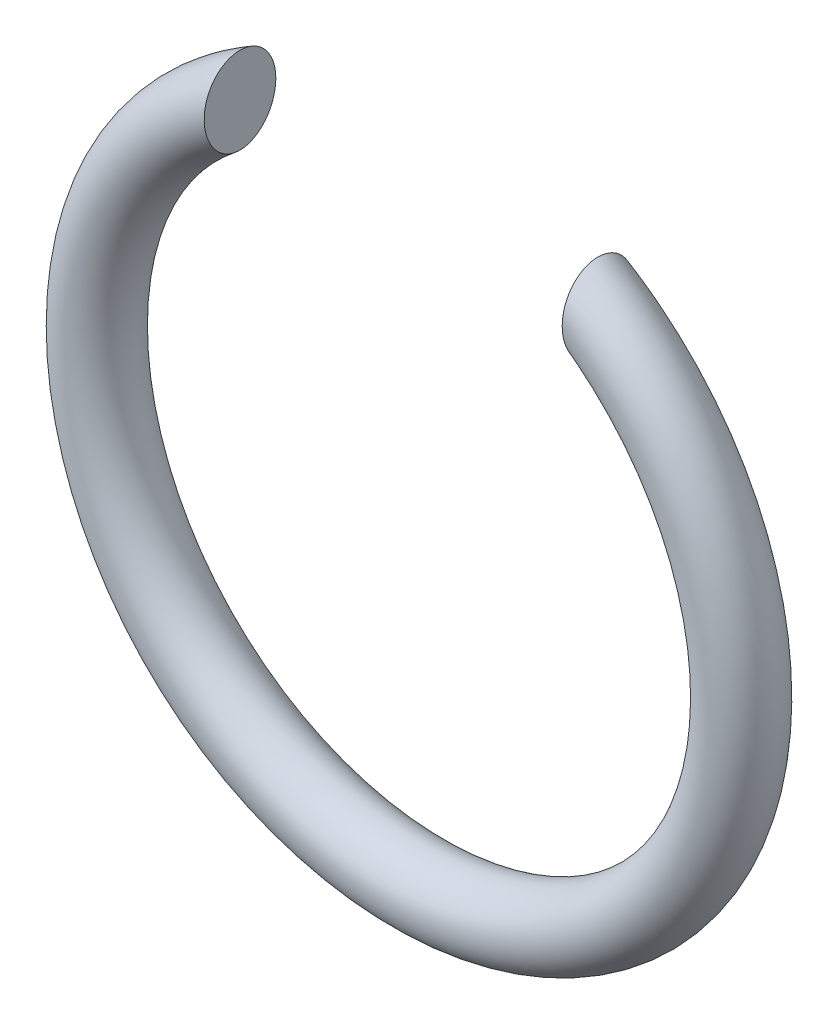
SolidWorks part; units mm, degrees
ref_plane "Front" through (0, 0, 0) normal (0, 0, 1) x (1, 0, 0)
ref_plane "Top" through (0, 0, 0) normal (0, 1, 0) x (1, 0, 0)
ref_plane "Right" through (0, 0, 0) normal (1, 0, 0) x (0, 0, -1)
sketch "Sketch1" plane through (0, 0, 0) normal (0, 0, 1) x (1, 0, 0)
  circle A1 centre (0, 0) radius 3.6
  dimension "D1" = 7.2
sketch "Sketch2" plane through (0, 0, 0) normal (0, 1, 0) x (1, 0, 0)
  circle A0 centre (3.6, 0) radius 0.4
  dimension "d1" = 0.8
sweep "Base-Sweep" add profiles "Sketch2" path "Sketch1"
sketch "Sketch3" plane through (0, 0, 0) normal (0, 0, 1) x (1, 0, 0)
  line L1 (-2, 0) -> (2, 0)
  line L2 (-2, 0) -> (-2, 4)
  line L3 (-2, 4) -> (2, 4)
  line L4 (2, 0) -> (2, 4)
  dimension "B/2" = 2
  dimension "D3" = 4
extrude "Cut-Extrude1" cut sketch "Sketch3" against normal through all and the other way through all
equation "\"B/2@Sketch3\" = \"B@Sketch3\" / 2"
